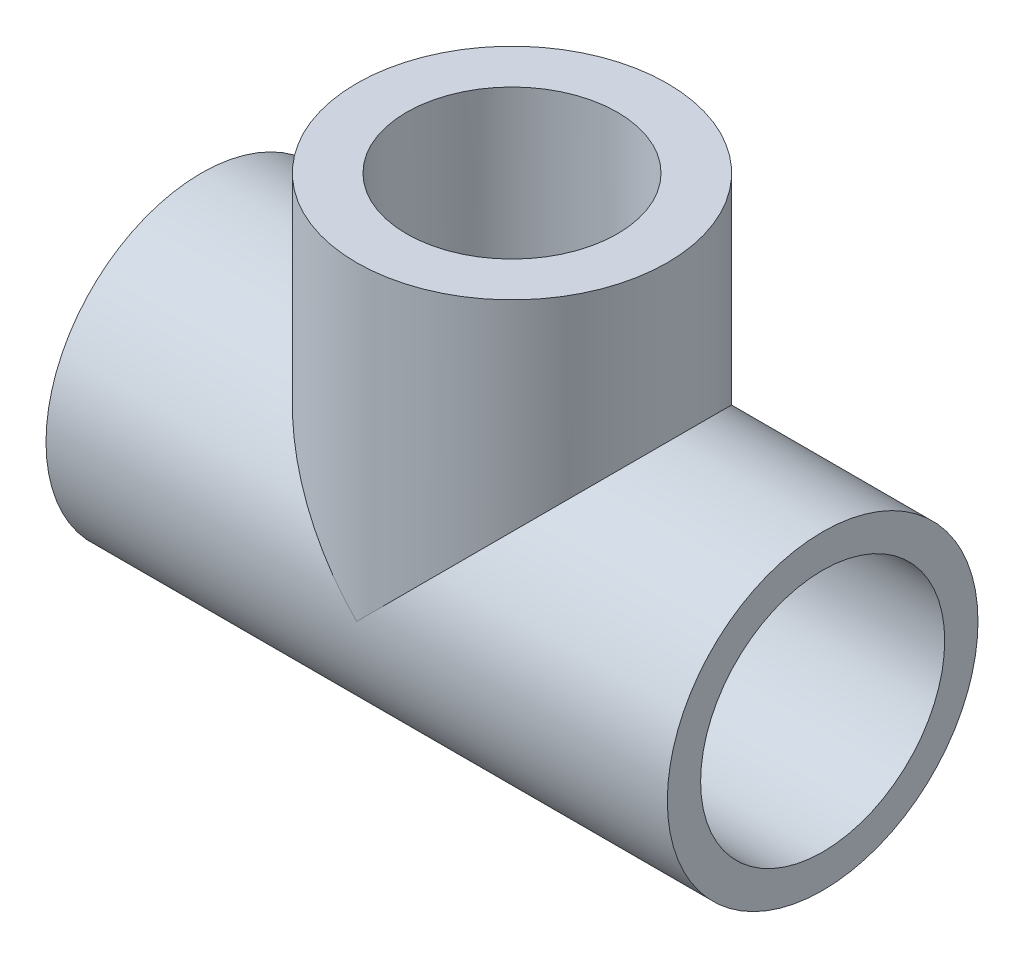
SolidWorks part; units mm, degrees
material "PVC Rigid"
ref_plane "Front Plane" through (0, 0, 0) normal (0, 0, 1) x (1, 0, 0)
ref_plane "Top Plane" through (0, 0, 0) normal (0, 1, 0) x (1, 0, 0)
ref_plane "Right Plane" through (0, 0, 0) normal (1, 0, 0) x (0, 0, -1)
sketch "Sketch1" plane through (0, 0, 0) normal (0, 1, 0) x (1, 0, 0)
  circle A0 centre (0, 0) radius 21.336
  dimension "D1" = 42.672
extrude "Boss-Extrude1" add sketch "Sketch1" along normal blind 42.672
sketch "Sketch2" plane through (0, 0, 0) normal (1, 0, 0) x (0, 0, -1)
  circle A0 centre (0, 0) radius 21.336
extrude "Boss-Extrude2" add sketch "Sketch2" along normal blind 42.672 and the other way blind 42.672
sketch "Sketch3" plane through (0, 42.672, 0) normal (0, 1, 0) x (1, 0, 0)
  circle A0 centre (0, 0) radius 14.478
  dimension "D1" = 28.956
extrude "Cut-Extrude1" cut sketch "Sketch3" against normal blind 42.672
sketch "Sketch6" plane through (42.672, 0, 0) normal (1, 0, 0) x (0, 0, -1)
  circle A0 centre (0, 0) radius 15.494
  dimension "D1" = 30.988
extrude "Cut-Extrude3" cut sketch "Sketch6" against normal up to surface (85.344 mm away) up to face at (-42.672, 0, -21.336)
sketch "Sketch4" plane through (42.672, 0, 0) normal (1, 0, 0) x (0, 0, -1)
  circle A0 centre (0, 0) radius 16.764
  dimension "D1" = 33.528
extrude "Cut-Extrude2" cut sketch "Sketch4" against normal blind 25.4
mirror "Mirror1" about plane through (0, 0, 0) normal (1, 0, 0) of "Cut-Extrude2"
